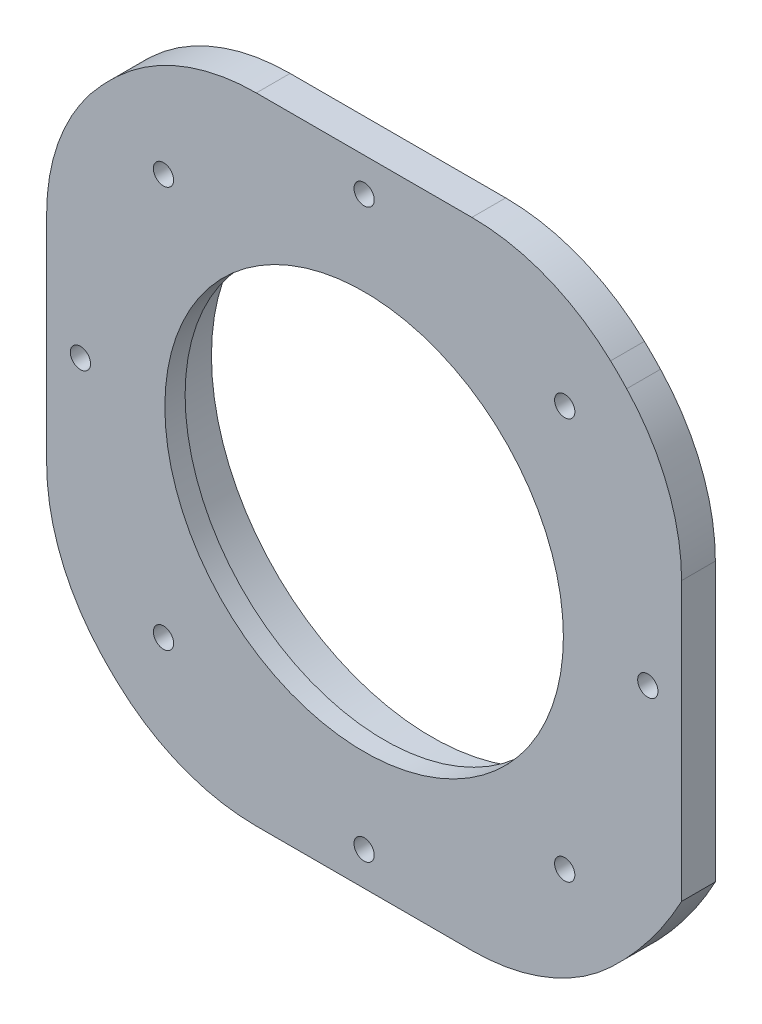
SolidWorks part; units mm, degrees
ref_plane "Front Plane" through (0, 0, 0) normal (0, 0, 1) x (1, 0, 0)
ref_plane "Top Plane" through (0, 0, 0) normal (0, 1, 0) x (1, 0, 0)
ref_plane "Right Plane" through (0, 0, 0) normal (1, 0, 0) x (0, 0, -1)
sketch "Sketch1" plane through (0, 0, 0) normal (0, 0, 1) x (1, 0, 0)
  line L4 (-47, 15.9577) -> (-47, -15.9577)
  line L5 (-15.9577, -47) -> (15.9577, -47)
  line L6 (47, -25.1719) -> (47, 15.9577)
  line L7 (15.9577, 47) -> (-15.9577, 47)
  circle A1 centre (0, 0) radius 36
  arc A2 (32.6244, 15.22) -> (34.2676, 11.0331) centre (33.5115, 13.1523) ccw
  arc A4 (26.6888, 24.1601) -> (29.4931, 20.6435) centre (28.1459, 22.4456) ccw
  arc A6 (18.3818, 30.9534) -> (22.098, 28.4196) centre (20.2795, 29.7446) ccw
  arc A8 (8.4415, 34.9963) -> (12.7395, 33.6706) centre (10.6112, 34.4006) ccw
  arc A10 (-2.2489, 35.9297) -> (2.2489, 35.9297) centre (0, 36) ccw
  arc A12 (-12.7395, 33.6706) -> (-8.4415, 34.9963) centre (-10.6112, 34.4006) ccw
  arc A14 (-22.098, 28.4196) -> (-18.3818, 30.9534) centre (-20.2795, 29.7446) ccw
  arc A16 (-29.4931, 20.6435) -> (-26.6888, 24.1601) centre (-28.1459, 22.4456) ccw
  arc A18 (-34.2676, 11.0331) -> (-32.6244, 15.22) centre (-33.5115, 13.1523) ccw
  arc A20 (-35.9973, 0.4424) -> (-35.6612, 4.9276) centre (-35.8993, 2.6903) ccw
  arc A22 (-34.5284, -10.1876) -> (-35.5293, -5.8026) centre (-35.0974, -8.0108) ccw
  arc A24 (-29.9916, -19.9124) -> (-32.2405, -16.0172) centre (-31.1769, -18) ccw
  arc A26 (-22.7898, -27.868) -> (-26.087, -24.8087) centre (-24.4862, -26.3899) ccw
  arc A28 (-13.5631, -33.3473) -> (-17.6155, -31.3958) centre (-15.6198, -32.4349) ccw
  arc A30 (-3.1313, -35.8636) -> (-7.5788, -35.1932) centre (-5.3655, -35.5979) ccw
  arc A32 (7.5788, -35.1932) -> (3.1313, -35.8636) centre (5.3655, -35.5979) ccw
  arc A34 (17.6155, -31.3958) -> (13.5631, -33.3473) centre (15.6198, -32.4349) ccw
  arc A36 (26.087, -24.8087) -> (22.7898, -27.868) centre (24.4862, -26.3899) ccw
  arc A38 (32.2405, -16.0172) -> (29.9916, -19.9124) centre (31.1769, -18) ccw
  arc A40 (35.5293, -5.8026) -> (34.5284, -10.1876) centre (35.0974, -8.0108) ccw
  arc A42 (35.6612, 4.9276) -> (35.9973, 0.4424) centre (35.8993, 2.6903) ccw
  arc A46 (32.7, 0) -> (-32.7, 0) centre (0, 0) ccw
  arc A47 (-32.7, 0) -> (32.7, 0) centre (0, 0) ccw
  arc A225 (-36.4898, 38.8731) -> (-38.8731, 36.4898) centre (0, 0) ccw
  arc A226 (-38.8731, 36.4898) -> (-47, 15.9577) centre (-17, 15.9577) ccw
  arc A227 (-47, -15.9577) -> (-38.8731, -36.4898) centre (-17, -15.9577) ccw
  arc A228 (-38.8731, -36.4898) -> (-36.4898, -38.8731) centre (0, 0) ccw
  arc A229 (-36.4898, -38.8731) -> (-15.9577, -47) centre (-15.9577, -17) ccw
  arc A230 (15.9577, -47) -> (36.4898, -38.8731) centre (15.9577, -17) ccw
  arc A231 (36.4898, -38.8731) -> (47, -25.1719) centre (0, 0) ccw
  arc A232 (47, 15.9577) -> (38.8731, 36.4898) centre (17, 15.9577) ccw
  arc A233 (38.8731, 36.4898) -> (36.4898, 38.8731) centre (0, 0) ccw
  arc A234 (36.4898, 38.8731) -> (15.9577, 47) centre (15.9577, 17) ccw
  arc A235 (-15.9577, 47) -> (-36.4898, 38.8731) centre (-15.9577, 17) ccw
extrude "Boss-Extrude1" add sketch "Sketch1" along normal blind 5 contours L7 A235 A225 A226 L4 A227 A228 A229 L5 A230 A231 L6 A232 A233 A234 A1 | A42 A1 A2 A4 A6 A8 A10 A12 A14 A16 A18 A20 A22 A24 A26 A28 A30 A32 A34 A36 A38 A40 A47 A46 | A46 A47 region at (-43.6583, 26.5094, 0) region at (34.8677, -2.8285, 0) region at (0, 0, 0)
extrude "Boss-Extrude2" add sketch "Sketch1<4>" against normal blind 5 contours A42 A1 A2 A4 A6 A8 A10 A12 A14 A16 A18 A20 A22 A24 A26 A28 A30 A32 A34 A36 A38 A40 A47 A46 region at (34.8677, -2.8285, 0)
sketch "Sketch1<4>" plane through (0, 0, 0) normal (0, 0, 1) x (1, 0, 0) same geometry as "Sketch1"
sketch "Sketch2" plane through (0, 0, 5) normal (0, 0, 1) x (1, 0, 0)
  line L4 (15.9577, 47) -> (-15.9577, 47)
  line L5 (-47, 15.9577) -> (-47, -15.9577)
  line L6 (-15.9577, -47) -> (15.9577, -47)
  line L7 (47, -25.1719) -> (47, 15.9577)
  line L8 (15.9577, 47) -> (-15.9577, 47)
  line L9 (-47, 15.9577) -> (-47, -15.9577)
  line L10 (-15.9577, -47) -> (15.9577, -47)
  line L11 (47, -25.1719) -> (47, 15.9577)
  arc A11 (-15.9577, 47) -> (-36.4898, 38.8731) centre (-15.9577, 17) ccw
  arc A12 (-36.4898, 38.8731) -> (-38.8731, 36.4898) centre (0, 0) ccw
  arc A13 (-38.8731, 36.4898) -> (-47, 15.9577) centre (-17, 15.9577) ccw
  arc A14 (-47, -15.9577) -> (-38.8731, -36.4898) centre (-17, -15.9577) ccw
  arc A15 (-38.8731, -36.4898) -> (-36.4898, -38.8731) centre (0, 0) ccw
  arc A16 (-36.4898, -38.8731) -> (-15.9577, -47) centre (-15.9577, -17) ccw
  arc A17 (15.9577, -47) -> (36.4898, -38.8731) centre (15.9577, -17) ccw
  arc A18 (36.4898, -38.8731) -> (47, -25.1719) centre (0, 0) ccw
  arc A19 (47, 15.9577) -> (38.8731, 36.4898) centre (17, 15.9577) ccw
  arc A20 (38.8731, 36.4898) -> (36.4898, 38.8731) centre (0, 0) ccw
  arc A21 (36.4898, 38.8731) -> (15.9577, 47) centre (15.9577, 17) ccw
  arc A22 (-15.9577, 47) -> (-36.4898, 38.8731) centre (-15.9577, 17) ccw
  arc A23 (-36.4898, 38.8731) -> (-38.8731, 36.4898) centre (0, 0) ccw
  arc A24 (-38.8731, 36.4898) -> (-47, 15.9577) centre (-17, 15.9577) ccw
  arc A25 (-47, -15.9577) -> (-38.8731, -36.4898) centre (-17, -15.9577) ccw
  arc A26 (-38.8731, -36.4898) -> (-36.4898, -38.8731) centre (0, 0) ccw
  arc A27 (-36.4898, -38.8731) -> (-15.9577, -47) centre (-15.9577, -17) ccw
  arc A28 (15.9577, -47) -> (36.4898, -38.8731) centre (15.9577, -17) ccw
  arc A29 (36.4898, -38.8731) -> (47, -25.1719) centre (0, 0) ccw
  arc A30 (47, 15.9577) -> (38.8731, 36.4898) centre (17, 15.9577) ccw
  arc A31 (38.8731, 36.4898) -> (36.4898, 38.8731) centre (0, 0) ccw
  arc A32 (36.4898, 38.8731) -> (15.9577, 47) centre (15.9577, 17) ccw
  dimension "D1" = 0
extrude "Boss-Extrude3" add sketch "Sketch2" against normal up to surface (5 mm away) up to face at (0, 0, 0)
sketch "Sketch3" plane through (0, 0, 0) normal (0, 0, -1) x (-1, 0, 0)
  circle A0 centre (0, 0) radius 32.6
  circle A1 centre (0, 0) radius 32.7
  circle A2 centre (0, 0) radius 32.7
  dimension "D1" = 0
  dimension "D2" = 0.1
extrude "Boss-Extrude4" add sketch "Sketch3" along normal up to surface (5 mm away) up to face at (32.7, 0, -5)
sketch "Sketch4" plane through (0, 0, 5) normal (0, 0, 1) x (1, 0, 0)
  line L4 (15.9577, 47) -> (-15.9577, 47)
  line L5 (-47, 15.9577) -> (-47, -15.9577)
  line L6 (-15.9577, -47) -> (15.9577, -47)
  line L7 (47, -25.1719) -> (47, 15.9577)
  line L8 (15.9577, 47) -> (-15.9577, 47)
  line L9 (-47, 15.9577) -> (-47, -15.9577)
  line L10 (-15.9577, -47) -> (15.9577, -47)
  line L11 (47, -25.1719) -> (47, 15.9577)
  circle A0 centre (0, 0) radius 32.6
  arc A11 (-15.9577, 47) -> (-36.4898, 38.8731) centre (-15.9577, 17) ccw
  arc A12 (-36.4898, 38.8731) -> (-38.8731, 36.4898) centre (0, 0) ccw
  arc A13 (-38.8731, 36.4898) -> (-47, 15.9577) centre (-17, 15.9577) ccw
  arc A14 (-47, -15.9577) -> (-38.8731, -36.4898) centre (-17, -15.9577) ccw
  arc A15 (-38.8731, -36.4898) -> (-36.4898, -38.8731) centre (0, 0) ccw
  arc A16 (-36.4898, -38.8731) -> (-15.9577, -47) centre (-15.9577, -17) ccw
  arc A17 (15.9577, -47) -> (36.4898, -38.8731) centre (15.9577, -17) ccw
  arc A18 (36.4898, -38.8731) -> (47, -25.1719) centre (0, 0) ccw
  arc A19 (47, 15.9577) -> (38.8731, 36.4898) centre (17, 15.9577) ccw
  arc A20 (38.8731, 36.4898) -> (36.4898, 38.8731) centre (0, 0) ccw
  arc A21 (36.4898, 38.8731) -> (15.9577, 47) centre (15.9577, 17) ccw
  arc A22 (-15.9577, 47) -> (-36.4898, 38.8731) centre (-15.9577, 17) ccw
  arc A23 (-36.4898, 38.8731) -> (-38.8731, 36.4898) centre (0, 0) ccw
  arc A24 (-38.8731, 36.4898) -> (-47, 15.9577) centre (-17, 15.9577) ccw
  arc A25 (-47, -15.9577) -> (-38.8731, -36.4898) centre (-17, -15.9577) ccw
  arc A26 (-38.8731, -36.4898) -> (-36.4898, -38.8731) centre (0, 0) ccw
  arc A27 (-36.4898, -38.8731) -> (-15.9577, -47) centre (-15.9577, -17) ccw
  arc A28 (15.9577, -47) -> (36.4898, -38.8731) centre (15.9577, -17) ccw
  arc A29 (36.4898, -38.8731) -> (47, -25.1719) centre (0, 0) ccw
  arc A30 (47, 15.9577) -> (38.8731, 36.4898) centre (17, 15.9577) ccw
  arc A31 (38.8731, 36.4898) -> (36.4898, 38.8731) centre (0, 0) ccw
  arc A32 (36.4898, 38.8731) -> (15.9577, 47) centre (15.9577, 17) ccw
  dimension "D2" = 65.2
  dimension "D1" = 0
extrude "Cut-Extrude1" cut sketch "Sketch4" against normal through all both contours A0 region at (0, 0, 5)
sketch "Sketch5" plane through (0, 0, 5) normal (0, 0, 1) x (1, 0, 0)
  line L4 (15.9577, 47) -> (-15.9577, 47)
  line L5 (-47, 15.9577) -> (-47, -15.9577)
  line L6 (-15.9577, -47) -> (15.9577, -47)
  line L7 (47, -25.1719) -> (47, 15.9577)
  line L8 (15.9577, 47) -> (-15.9577, 47)
  line L9 (-47, 15.9577) -> (-47, -15.9577)
  line L10 (-15.9577, -47) -> (15.9577, -47)
  line L11 (47, -25.1719) -> (47, 15.9577)
  circle A0 centre (0, 0) radius 29.5
  arc A12 (-15.9577, 47) -> (-36.4898, 38.8731) centre (-15.9577, 17) ccw
  arc A13 (-36.4898, 38.8731) -> (-38.8731, 36.4898) centre (0, 0) ccw
  arc A14 (-38.8731, 36.4898) -> (-47, 15.9577) centre (-17, 15.9577) ccw
  arc A15 (-47, -15.9577) -> (-38.8731, -36.4898) centre (-17, -15.9577) ccw
  arc A16 (-38.8731, -36.4898) -> (-36.4898, -38.8731) centre (0, 0) ccw
  arc A17 (-36.4898, -38.8731) -> (-15.9577, -47) centre (-15.9577, -17) ccw
  arc A18 (15.9577, -47) -> (36.4898, -38.8731) centre (15.9577, -17) ccw
  arc A19 (36.4898, -38.8731) -> (47, -25.1719) centre (0, 0) ccw
  arc A20 (47, 15.9577) -> (38.8731, 36.4898) centre (17, 15.9577) ccw
  arc A21 (38.8731, 36.4898) -> (36.4898, 38.8731) centre (0, 0) ccw
  arc A22 (36.4898, 38.8731) -> (15.9577, 47) centre (15.9577, 17) ccw
  arc A23 (-15.9577, 47) -> (-36.4898, 38.8731) centre (-15.9577, 17) ccw
  arc A24 (-36.4898, 38.8731) -> (-38.8731, 36.4898) centre (0, 0) ccw
  arc A25 (-38.8731, 36.4898) -> (-47, 15.9577) centre (-17, 15.9577) ccw
  arc A26 (-47, -15.9577) -> (-38.8731, -36.4898) centre (-17, -15.9577) ccw
  arc A27 (-38.8731, -36.4898) -> (-36.4898, -38.8731) centre (0, 0) ccw
  arc A28 (-36.4898, -38.8731) -> (-15.9577, -47) centre (-15.9577, -17) ccw
  arc A29 (15.9577, -47) -> (36.4898, -38.8731) centre (15.9577, -17) ccw
  arc A30 (36.4898, -38.8731) -> (47, -25.1719) centre (0, 0) ccw
  arc A31 (47, 15.9577) -> (38.8731, 36.4898) centre (17, 15.9577) ccw
  arc A32 (38.8731, 36.4898) -> (36.4898, 38.8731) centre (0, 0) ccw
  arc A33 (36.4898, 38.8731) -> (15.9577, 47) centre (15.9577, 17) ccw
  dimension "D1" = 59
  dimension "D2" = 0
extrude "Boss-Extrude5" add sketch "Sketch5" against normal offset from surface (3 mm away) 7 up to face at (0, 0, -5)
sketch "Sketch6" plane through (0, 0, 5) normal (0, 0, 1) x (1, 0, 0)
  circle A0 centre (42, 0) radius 1.5
  circle A1 centre (29.6985, -29.6985) radius 1.5
  circle A2 centre (0, -42) radius 1.5
  circle A3 centre (-29.6985, -29.6985) radius 1.5
  circle A4 centre (-42, 0) radius 1.5
  circle A5 centre (-29.6985, 29.6985) radius 1.5
  circle A6 centre (0, 42) radius 1.5
  circle A7 centre (29.6985, 29.6985) radius 1.5
  point P45 (0, 0)
  dimension "D2" = 3
  dimension "D4" = 8
extrude "Cut-Extrude3" cut sketch "Sketch6" against normal through all both and the other way through all
